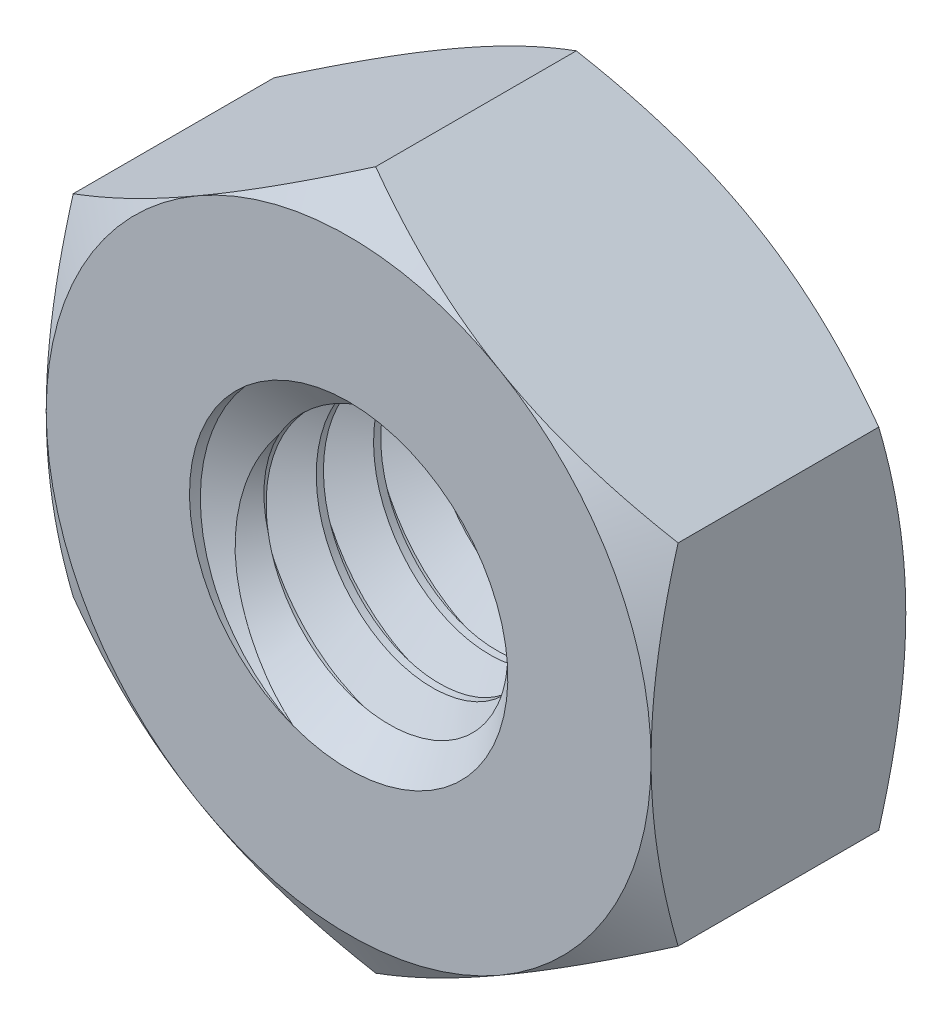
SolidWorks part; units mm, degrees
ref_plane "Front" through (0, 0, 0) normal (0, 0, 1) x (1, 0, 0)
ref_plane "Top" through (0, 0, 0) normal (0, 1, 0) x (1, 0, 0)
ref_plane "Right" through (0, 0, 0) normal (1, 0, 0) x (0, 0, -1)
sketch "Sketch1" plane through (0, 0, 0) normal (0, 0, 1) x (1, 0, 0)
  line L1 (-2.375, 1.3712) -> (-2.375, -1.3712)
  line L2 (-2.375, -1.3712) -> (0, -2.7424)
  line L3 (0, -2.7424) -> (2.375, -1.3712)
  line L4 (2.375, -1.3712) -> (2.375, 1.3712)
  line L5 (2.375, 1.3712) -> (0, 2.7424)
  line L6 (0, 2.7424) -> (-2.375, 1.3712)
  circle A0 centre (0, 0) radius 2.375 construction
  circle A1 centre (0, 0) radius 1.25 construction
  point P10 (0, 1.25)
  dimension "hex" = 4.75
  dimension "dia" = 2.5
extrude "Extrude1" add sketch "Sketch1" along normal mid plane 2
sketch "Sketch4" plane through (0, 0, -1) normal (0, 0, -1) x (-1, 0, 0)
  circle A0 centre (0, 0) radius 1.25 construction
  circle A1 centre (0, 0) radius 1.25
sketch "Sketch10" plane through (0, 0, 1) normal (0, 0, 1) x (1, 0, 0)
  circle A0 centre (0, 0) radius 1.25 construction
  circle A1 centre (0, 0) radius 1.25
extrude "Cut-Extrude2" cut sketch "Sketch10" against normal through all draft 45
sketch "Sketch11" plane through (0, 0, -1) normal (0, 0, -1) x (-1, 0, 0)
  circle A0 centre (0, 0) radius 1.25 construction
  circle A1 centre (0, 0) radius 1.25
extrude "Cut-Extrude3" cut sketch "Sketch11" against normal through all draft 45
sketch "Sketch13" plane through (0, 0, -1) normal (0, 0, -1) x (-1, 0, 0)
  circle A0 centre (0, 0) radius 1.25 construction
  circle A1 centre (0, 0) radius 1.25
extrude "Boss-Extrude1" add sketch "Sketch13" against normal up to vertex (2 mm away) separate body up to point (-2.375, 1.3712, 1)
curve "Helix/Spiral3" pitch 0.45 height 2 turns 4.4444
sketch "Sketch12" plane through (0, 0, 0) normal (1, 0, 0) x (0, 0, -1)
  line L0 (1.3937, 1.25) -> (1, 1.25)
  line L1 (1.3937, 1.25) -> (1.225, 0.9577)
  line L2 (1.225, 0.9577) -> (1.1687, 0.9577)
  line L3 (1.1687, 0.9577) -> (1, 1.25)
  line L4 (1.1969, 0.9577) -> (1.1969, 1.25) construction
  line L5 (1.0844, 1.1039) -> (1.3094, 1.1039) construction
  dimension "D1" = 60
  dimension "D2" = 0.0563
  dimension "D3" = 0.225
sweep "Cut-Sweep1" cut profiles "Sketch12" path "Helix/Spiral3"
combine bodies "Combine1" operation type subtract main body 116 bodies to subtract 118
sketch "Sketch7" plane through (0, 0, 1) normal (0, 0, 1) x (1, 0, 0)
  circle A0 centre (0, 0) radius 2.375 construction
  circle A1 centre (0, 0) radius 2.375
extrude "Extrude2" cut sketch "Sketch7" against normal blind 25.4 draft 60 flip side to cut
mirror "Mirror2" about plane through (0, 0, 0) normal (0, 0, 1) of "Extrude2"
sketch "Sketch8" plane through (0, 0, 1) normal (0, 0, 1) x (1, 0, 0)
  line L0 (-0.8839, 0.8839) -> (0, 0) construction
  line L1 (0, -55) -> (0, 55) construction
  circle A1 centre (0, 0) radius 1.25 construction
  point P0 (-0.8839, 0.8839)
  dimension "D1" = 45
sketch "Sketch14" plane through (0, 0, 1) normal (0, 0, 1) x (1, 0, 0)
  line L0 (0, 0) -> (-1.25, 0) construction
  arc A0 (0, 1.25) -> (-0.4358, -1.1716) centre (0, 0) ccw construction
equation "\"D3@Helix/Spiral3\" = \"length@Extrude1\" "
equation "\"D2@Sketch12\" = \"D4@Helix/Spiral3\"*.125"
equation "\"D3@Sketch12\" = \"D4@Helix/Spiral3\"*.50"
